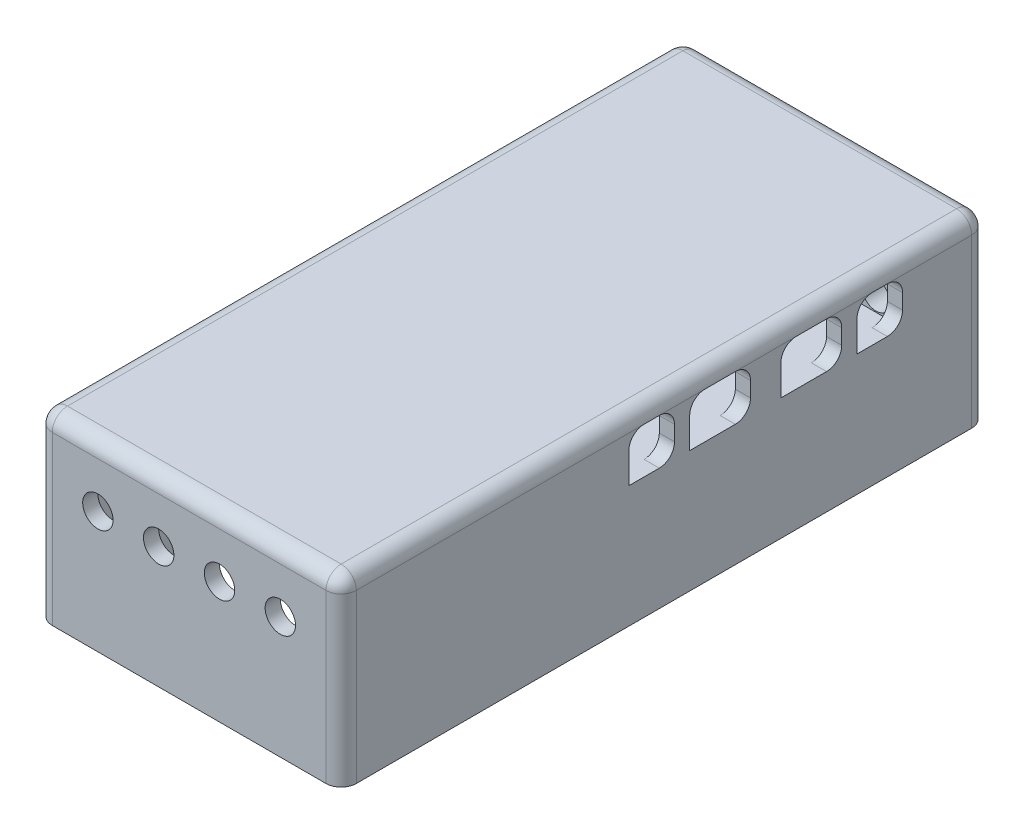
SolidWorks part; units mm, degrees
ref_plane "Front Plane" through (0, 0, 0) normal (0, 0, 1) x (1, 0, 0)
ref_plane "Top Plane" through (0, 0, 0) normal (0, 1, 0) x (1, 0, 0)
ref_plane "Right Plane" through (0, 0, 0) normal (1, 0, 0) x (0, 0, -1)
sketch "Sketch1" plane through (95.1651, 0, 0) normal (1, 0, 0) x (0, 0, -1)
  line L0 (34.2862, -5.0634) -> (16.2862, -5.0634)
  line L1 (16.2862, -5.0634) -> (16.2862, -1.0634)
  line L2 (16.2862, -1.0634) -> (-0.6388, -1.0634)
  line L4 (0.2424, -0.0634) -> (19.1505, -0.0634)
  line L5 (17.2862, -1.0634) -> (17.2862, -4.0634)
  line L6 (17.2862, -4.0634) -> (35.2862, -4.0634)
  line L7 (35.2862, -4.0634) -> (35.2862, -12.0634)
  line L8 (35.2862, -12.0634) -> (34.2862, -12.0634)
  line L9 (34.2862, -5.0634) -> (34.2862, -12.0634)
  line L10 (39.0366, -1.0634) -> (39.0366, -12.0634)
  line L11 (19.1505, -0.0634) -> (40.8366, -0.0634)
  line L12 (39.0366, -12.0634) -> (40.8366, -12.0634)
  line L13 (17.2862, -1.0634) -> (39.0366, -1.0634)
  line L14 (0.2424, -0.0634) -> (-1.6388, -0.0634)
  line L15 (40.8366, -12.0634) -> (40.8366, -0.0634)
  line L16 (-1.6388, -0.0634) -> (-1.6388, -12.0634)
  line L17 (-1.6388, -12.0634) -> (-0.6388, -12.0634)
  line L18 (-0.6388, -12.0634) -> (-0.6388, -1.0634)
  dimension "D2" = 1
  dimension "D3" = 1
  dimension "D4" = 7
  dimension "D5" = 1
  dimension "D6" = 4
  dimension "D7" = 1
  dimension "D8" = 18
  dimension "D9" = 1.8
  dimension "D10" = 3
  dimension "D11" = 1
  dimension "D12" = 34.925
extrude "Boss-Extrude1" add sketch "Sketch1" along normal blind 18 contours L9 L8 L7 L6 L5 L13 L10 L12 L15 L11 L4 L14 L16 L17 L18 L2 L1 L0
sketch "Sketch2" plane through (0, 0, -40.8366) normal (0, 0, -1) x (-1, 0, 0)
  line L0 (-108.6651, -6.8134) -> (-99.6651, -6.8134) construction
  line L1 (-104.1651, -0.0634) -> (-104.1651, -12.0634) construction
  line L2 (-113.1651, -0.0634) -> (-95.1651, -0.0634) construction
  line L3 (-113.1651, -12.0634) -> (-95.1651, -12.0634) construction
  line L4 (-113.1651, -1.0634) -> (-95.1651, -1.0634) construction
  line L5 (-107.1055, -6.0196) -> (-105.0001, -6.0196)
  line L6 (-103.3301, -6.0196) -> (-101.2247, -6.0196)
  line L7 (-112.3301, -7.6071) -> (-110.2247, -7.6071)
  line L8 (-112.3301, -6.0196) -> (-110.2247, -6.0196)
  line L9 (-103.3301, -7.6071) -> (-101.2247, -7.6071)
  line L10 (-107.1055, -7.6071) -> (-105.0001, -7.6071)
  line L11 (-98.1055, -6.0196) -> (-96.0001, -6.0196)
  line L12 (-98.4999, -7.6071) -> (-96.0001, -7.6071)
  arc A0 (-112.3301, -7.6071) -> (-105.0001, -7.6071) centre (-108.6651, -6.8134) ccw
  arc A1 (-103.3301, -7.6071) -> (-96.0001, -7.6071) centre (-99.6651, -6.8134) ccw
  arc A2 (-110.2247, -7.6071) -> (-107.1055, -7.6071) centre (-108.6651, -6.8134) ccw
  circle A3 centre (-108.6651, -6.8134) radius 0.925
  arc A4 (-107.1055, -6.0196) -> (-110.2247, -6.0196) centre (-108.6651, -6.8134) ccw
  arc A5 (-105.0001, -6.0196) -> (-112.3301, -6.0196) centre (-108.6651, -6.8134) ccw
  circle A6 centre (-99.6651, -6.8134) radius 0.925
  arc A7 (-101.2247, -7.6071) -> (-98.1055, -7.6071) centre (-99.6651, -6.8134) ccw
  arc A8 (-98.1055, -6.0196) -> (-101.2247, -6.0196) centre (-99.6651, -6.8134) ccw
  arc A9 (-96.0001, -6.0196) -> (-103.3301, -6.0196) centre (-99.6651, -6.8134) ccw
  point P10 (-104.1651, -6.8134)
  dimension "D1" = 7.5
  dimension "D2" = 7.5
  dimension "D5" = 3.5
  dimension "D6" = 1.85
  dimension "D9" = 3.5
  dimension "D10" = 1.85
  dimension "D3" = 9
  dimension "D4" = 5.75
  dimension "D7" = 0.7937
  dimension "D8" = 0.7937
  dimension "D11" = 0.7937
  dimension "D12" = 0.7937
extrude "Cut-Extrude1" cut sketch "Sketch2" against normal blind 3 contours L5 A5 L8 A4 | A2 L7 A0 L10 | A3 | A6 | L11 A9 L6 A8 | A7 L9 A1 L12
sketch "Sketch4" plane through (113.1651, 0, 0) normal (1, 0, 0) x (0, 0, -1)
  line L1 (40.8366, -12.0634) -> (-1.6388, -12.0634)
  line L2 (40.8366, -12.0634) -> (40.8366, -0.0634)
  line L3 (40.8366, -0.0634) -> (-1.6388, -0.0634)
  line L4 (-1.6388, -12.0634) -> (-1.6388, -0.0634)
extrude "Boss-Extrude2" add sketch "Sketch4" along normal blind 1
sketch "Sketch5" plane through (95.1651, 0, 0) normal (-1, 0, 0) x (0, 0, 1)
  line L1 (-40.8366, -12.0634) -> (1.6388, -12.0634)
  line L2 (-40.8366, -12.0634) -> (-40.8366, -0.0634)
  line L3 (-40.8366, -0.0634) -> (1.6388, -0.0634)
  line L4 (1.6388, -12.0634) -> (1.6388, -0.0634)
extrude "Boss-Extrude3" add sketch "Sketch5" along normal blind 1
sketch "Sketch6" plane through (94.1651, 0, 0) normal (-1, 0, 0) x (0, 0, 1)
  line L0 (-17.2862, -4.0634) -> (-35.2862, -4.0634) construction
  line L1 (-17.2862, -1.0634) -> (-20.2862, -1.0634)
  line L2 (-17.2862, -1.0634) -> (-17.2862, -4.0634)
  line L3 (-17.2862, -4.0634) -> (-20.2862, -4.0634)
  line L4 (-20.2862, -1.0634) -> (-20.2862, -4.0634)
  line L5 (-17.2862, -1.0634) -> (-39.0366, -1.0634) construction
  line L6 (-21.2862, -1.0634) -> (-25.2862, -1.0634)
  line L7 (-21.2862, -1.0634) -> (-21.2862, -4.0634)
  line L8 (-21.2862, -4.0634) -> (-25.2862, -4.0634)
  line L9 (-25.2862, -1.0634) -> (-25.2862, -4.0634)
  line L11 (-27.2862, -1.0634) -> (-31.2862, -1.0634)
  line L12 (-27.2862, -1.0634) -> (-27.2862, -4.0634)
  line L13 (-27.2862, -4.0634) -> (-31.2862, -4.0634)
  line L14 (-31.2862, -1.0634) -> (-31.2862, -4.0634)
  line L15 (-35.2862, -1.0634) -> (-32.2862, -1.0634)
  line L16 (-35.2862, -1.0634) -> (-35.2862, -4.0634)
  line L17 (-35.2862, -4.0634) -> (-32.2862, -4.0634)
  line L18 (-32.2862, -1.0634) -> (-32.2862, -4.0634)
  dimension "D1" = 3
  dimension "D2" = 4
  dimension "D3" = 4
  dimension "D4" = 3
  dimension "D5" = 1
  dimension "D6" = 1
extrude "Cut-Extrude2" cut sketch "Sketch6" against normal through all
fillet "Fillet1" radius 1 23 edges at (113.6651, -1.0634, -32.2862) (113.6651, -1.0634, -27.2862) (113.6651, -1.0634, -21.2862) (113.6651, -1.0634, -35.2862) (113.6651, -1.0634, -31.2862) (113.6651, -1.0634, -25.2862) (113.6651, -1.0634, -20.2862) (113.6651, -4.0634, -35.2862) (113.6651, -4.0634, -31.2862) (113.6651, -4.0634, -25.2862) (113.6651, -4.0634, -20.2862) (104.1651, -1.0634, -17.2862) (94.6651, -1.0634, -20.2862) (94.6651, -4.0634, -20.2862) (94.6651, -1.0634, -21.2862) (94.6651, -1.0634, -25.2862) (94.6651, -4.0634, -25.2862) (94.6651, -4.0634, -31.2862) (94.6651, -1.0634, -31.2862) (94.6651, -1.0634, -27.2862) (94.6651, -4.0634, -35.2862) (94.6651, -1.0634, -35.2862) (94.6651, -1.0634, -32.2862)
fillet "Fillet2" radius 1 8 edges at (114.1651, -0.0634, -19.5989) (114.1651, -6.0634, 1.6388) (94.1651, -6.0634, 1.6388) (94.1651, -6.0634, -40.8366) (114.1651, -6.0634, -40.8366) (104.1651, -0.0634, 1.6388) (104.1651, -0.0634, -40.8366) (94.1651, -0.0634, -19.5989)
sketch "Sketch7" plane through (0, -4.0634, 0) normal (0, 1, 0) x (1, 0, 0)
  line L0 (113.1651, 34.2862) -> (95.1651, 34.2862) construction
  line L2 (95.1651, 39.8366) -> (95.1651, -0.6388) construction
  circle A0 centre (103.6651, 26.7862) radius 5
  dimension "D1" = 10
  dimension "D2" = 7.5
  dimension "D3" = 8.5
extrude "Cut-Extrude3" cut sketch "Sketch7" against normal blind 1 contours A0
sketch "Sketch8" plane through (0, 0, 1.6388) normal (0, 0, 1) x (1, 0, 0)
  line L0 (95.1651, -4.0634) -> (113.1651, -4.0634) construction
  line L1 (95.1651, -1.0634) -> (95.1651, -12.0634) construction
  line L2 (113.1651, -12.0634) -> (113.1651, -1.0634) construction
  line L3 (114.1651, -4.0634) -> (94.1651, -4.0634) construction
  circle A0 centre (98.1651, -4.0634) radius 1
  circle A1 centre (102.1651, -4.0634) radius 1
  circle A2 centre (106.1651, -4.0634) radius 1
  circle A3 centre (110.1651, -4.0634) radius 1
  dimension "D1" = 2
  dimension "D2" = 0
  dimension "D3" = 3
  dimension "D4" = 3
  dimension "D5" = 4
  dimension "D6" = 4
extrude "Cut-Extrude4" cut sketch "Sketch8" against normal blind 1
